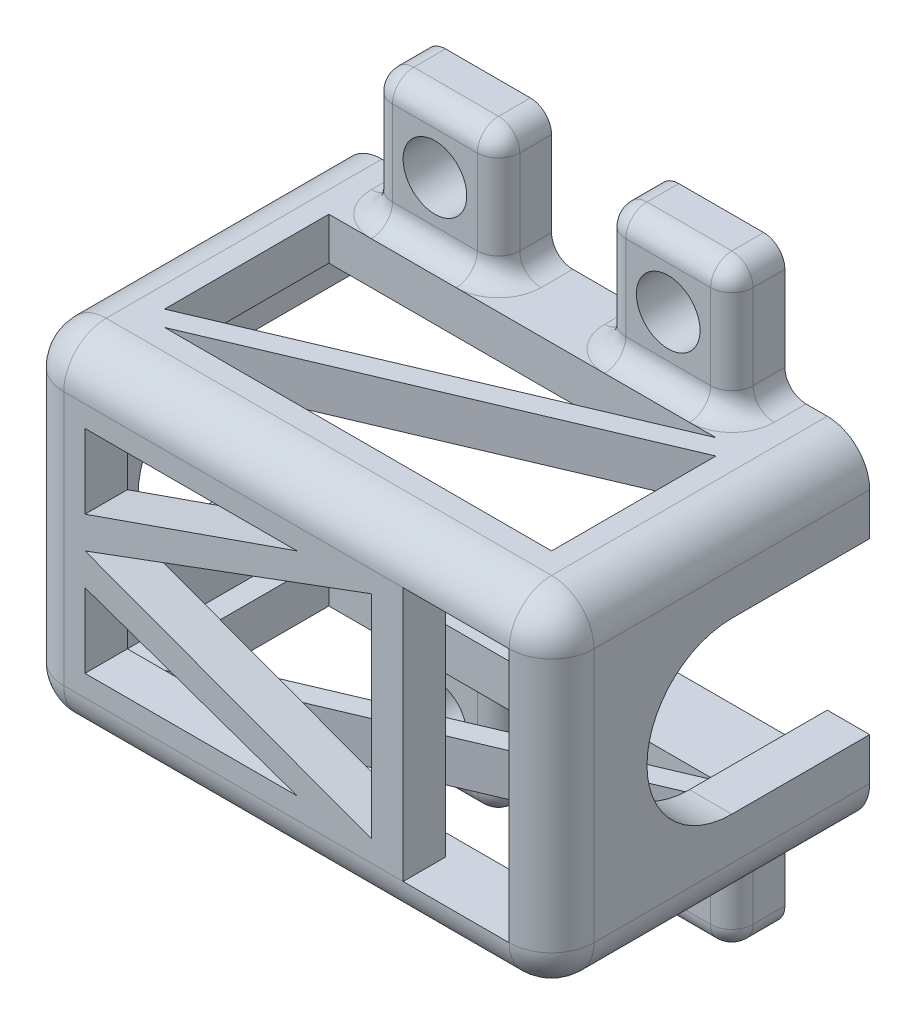
SolidWorks part; units mm, degrees
ref_plane "Alzado" through (0, 0, 0) normal (0, 0, 1) x (1, 0, 0)
ref_plane "Planta" through (0, 0, 0) normal (0, 1, 0) x (1, 0, 0)
ref_plane "Vista lateral" through (0, 0, 0) normal (1, 0, 0) x (0, 0, -1)
sketch "Croquis1" plane through (0, 0, 0) normal (0, 0, 1) x (1, 0, 0)
  line L1 (0, 0) -> (23, 0)
  line L2 (0, 0) -> (0, 16)
  line L3 (0, 16) -> (23, 16)
  line L4 (23, 0) -> (23, 16)
  dimension "D1" = 16
  dimension "D2" = 23
extrude "Saliente-Extruir1" add sketch "Croquis1" along normal blind 15
sketch "Croquis2" plane through (23, 0, 0) normal (1, 0, 0) x (0, 0, -1)
  line L0 (0, 0) -> (0, 16) construction
  line L1 (-13, 2) -> (-2, 2)
  line L2 (-13, 2) -> (-13, 14)
  line L3 (-13, 14) -> (-2, 14)
  line L4 (-2, 2) -> (-2, 14)
  line L5 (-15, 0) -> (-15, 16) construction
  line L6 (-15, 16) -> (0, 16) construction
  line L7 (-15, 0) -> (0, 0) construction
  dimension "D1" = 2
  dimension "D2" = 2
  dimension "D3" = 2
  dimension "D4" = 2
extrude "Cortar-Extruir1" cut sketch "Croquis2" against normal blind 21
sketch "Croquis4" plane through (0, 0, 0) normal (-1, 0, 0) x (0, 0, 1)
  line L0 (0, 0) -> (15, 16) construction
  line L1 (15, 16) -> (15, 0) construction
  line L2 (15, 16) -> (0, 16) construction
  line L3 (7.5, 12) -> (0, 12)
  line L4 (0, 16) -> (0, 0) construction
  line L5 (0, 12) -> (0, 4)
  line L6 (0, 4) -> (7.5, 4)
  arc A1 (7.5, 12) -> (7.5, 4) centre (7.5, 8) cw
  dimension "D1" = 4
  dimension "D3" = 8
  dimension "D2" = 7.5
extrude "Cortar-Extruir2" cut sketch "Croquis4" against normal blind 23
sketch "Croquis5" plane through (0, 0, 15) normal (0, 0, 1) x (1, 0, 0)
  line L0 (23, 0) -> (23, 16) construction
  line L1 (23, 2) -> (18, 2)
  line L2 (23, 2) -> (23, 14)
  line L3 (23, 14) -> (18, 14)
  line L4 (18, 2) -> (18, 14)
  line L5 (23, 16) -> (0, 16) construction
  line L6 (0, 0) -> (23, 0) construction
  dimension "D1" = 2
  dimension "D2" = 2
  dimension "D3" = 5
extrude "Cortar-Extruir3" cut sketch "Croquis5" against normal blind 2
fillet "Redondeo1" radius 2 5 edges at (11.5, 16, 15) (11.5, 0, 15) (0, 16, 7.5) (0, 8, 15) (0, 0, 7.5)
sketch "Croquis8" plane through (0, 0, 15) normal (0, 0, 1) x (1, 0, 0)
  line L0 (16.5, 3) -> (16.5, 13)
  line L1 (18, 14) -> (18, 2) construction
  line L2 (16.5, 8) -> (3, 8) construction
  line L3 (3, 8) -> (16.5, 3)
  line L4 (3, 8) -> (16.5, 13)
  line L6 (3, 8) -> (3, 6.5005) construction
  line L7 (3, 6.5005) -> (3, 3)
  line L8 (3, 3) -> (13, 3)
  line L9 (13, 3) -> (3, 6.5005)
  line L10 (3, 8) -> (3, 9.5) construction
  line L11 (3, 9.5) -> (3, 13)
  line L12 (3, 13) -> (13, 13)
  line L13 (13, 13) -> (3, 9.5)
  line L14 (18, 14) -> (2, 14) construction
  line L15 (2, 2) -> (18, 2) construction
  line L19 (2, 14) -> (2, 2) construction
  dimension "D1" = 1.5
  dimension "D2" = 1
  dimension "D3" = 1.4995
  dimension "D4" = 1.5
  dimension "D5" = 1
  dimension "D6" = 1
  dimension "D7" = 5
  dimension "D8" = 5
extrude "Cortar-Extruir4" cut sketch "Croquis8" against normal through all
sketch "Croquis18" plane through (0, 0, 2) normal (0, 0, 1) x (1, 0, 0)
  line L1 (2, 14) -> (23, 14)
  line L2 (2, 14) -> (2, 2)
  line L3 (2, 2) -> (23, 2)
  line L4 (23, 14) -> (23, 2)
extrude "Cortar-Extruir8" cut sketch "Croquis18" against normal through all
sketch "Croquis17" plane through (23, 0, 0) normal (1, 0, 0) x (0, 0, -1)
  line L1 (0, 0) -> (-15, 0)
  line L2 (0, 0) -> (0, 16)
  line L3 (0, 16) -> (-15, 16)
  line L4 (-15, 0) -> (-15, 16)
  dimension "D1" = 15
extrude "Saliente-Extruir7" add sketch "Croquis17" along normal blind 2
fillet "Redondeo8" radius 2 3 edges at (25, 0, 7.5) (25, 16, 7.5) (25, 8, 15)
sketch "Croquis19" plane through (0, 16, 0) normal (0, 1, 0) x (1, 0, 0)
  line L0 (23, 0) -> (2, 0) construction
  line L1 (21, 0) -> (15, 0)
  line L2 (21, 0) -> (21, -2.5)
  line L3 (21, -2.5) -> (15, -2.5)
  line L4 (15, 0) -> (15, -2.5)
  line L5 (23, -13) -> (23, 0) construction
  line L6 (4, 0) -> (10, 0)
  line L7 (4, 0) -> (4, -2.5)
  line L8 (4, -2.5) -> (10, -2.5)
  line L9 (10, 0) -> (10, -2.5)
  line L10 (2, 0) -> (2, -13) construction
  dimension "D1" = 2
  dimension "D2" = 2
  dimension "D3" = 2.5
  dimension "D4" = 2.5
  dimension "D5" = 6
  dimension "D6" = 6
extrude "Saliente-Extruir8" add sketch "Croquis19" along normal blind 6
sketch "Croquis20" plane through (0, 0, 0) normal (0, -1, 0) x (1, 0, 0)
  line L0 (2, 0) -> (23, 0) construction
  line L1 (4, 0) -> (10, 0)
  line L2 (4, 0) -> (4, 2.5)
  line L3 (4, 2.5) -> (10, 2.5)
  line L4 (10, 0) -> (10, 2.5)
  line L5 (2, 13) -> (2, 0) construction
  line L6 (21, 0) -> (15, 0)
  line L7 (21, 0) -> (21, 2.5)
  line L8 (21, 2.5) -> (15, 2.5)
  line L9 (15, 0) -> (15, 2.5)
  line L10 (23, 0) -> (23, 13) construction
  dimension "D1" = 2
  dimension "D2" = 2
  dimension "D3" = 2.5
  dimension "D4" = 2.5
  dimension "D5" = 6
  dimension "D6" = 6
extrude "Saliente-Extruir9" add sketch "Croquis20" along normal blind 6
sketch "Croquis21" plane through (0, 0, 2.5) normal (0, 0, 1) x (1, 0, 0)
  line L0 (4, 22) -> (10, 16) construction
  line L1 (15, 22) -> (21, 16) construction
  line L3 (21, 0) -> (15, -6) construction
  line L5 (10, 0) -> (4, -6) construction
  circle A0 centre (18, 19) radius 1.5
  circle A1 centre (7, 19) radius 1.5
  circle A2 centre (7, -3) radius 1.5
  circle A3 centre (18, -3) radius 1.5
  dimension "D1" = 3
  dimension "D2" = 3
  dimension "D3" = 3
  dimension "D4" = 3
extrude "Cortar-Extruir9" cut sketch "Croquis21" against normal through all
fillet "Redondeo9" radius 1 32 edges at (15, 0, 1.25) (21, 0, 1.25) (10, 0, 1.25) (4, 0, 1.25) (21, 16, 1.25) (15, 16, 1.25) (4, 16, 1.25) (10, 16, 1.25) (21, -6, 1.25) (15, -6, 1.25) (18, -6, 2.5) (15, -3, 2.5) (21, -3, 2.5) (18, 0, 2.5) (7, 0, 2.5) (10, -6, 1.25) (4, -6, 1.25) (4, -3, 2.5) (10, -3, 2.5) (7, -6, 2.5) (21, 22, 1.25) (15, 22, 1.25) (21, 19, 2.5) (18, 22, 2.5) (15, 19, 2.5) (18, 16, 2.5) (10, 22, 1.25) (4, 22, 1.25) (7, 16, 2.5) (4, 19, 2.5) (10, 19, 2.5) (7, 22, 2.5)
sketch "Croquis22" plane through (0, 0, 0) normal (0, -1, 0) x (1, 0, 0)
  line L1 (3, 3.5) -> (22, 3.5) construction
  line L6 (22, 3.5) -> (21.25, 3.5) construction
  line L9 (3, 4.25) -> (3, 3.5) construction
  line L10 (3, 3.5) -> (3.75, 3.5) construction
  line L12 (3, 11.25) -> (21.25, 3.5)
  line L13 (22, 11.25) -> (22, 12) construction
  line L14 (22, 12) -> (21.25, 12) construction
  line L15 (21.25, 3.5) -> (3, 3.5)
  line L16 (3, 3.5) -> (3, 11.25)
  line L17 (22, 4.25) -> (3.75, 12)
  line L18 (3.75, 12) -> (22, 12)
  line L19 (22, 12) -> (22, 4.25)
  line L20 (2, 13) -> (2, 0) construction
  line L21 (23, 0) -> (23, 13) construction
  line L22 (23, 13) -> (2, 13) construction
  line L23 (11, 0) -> (14, 0) construction
  point P5 (0, 0)
  dimension "D1" = 1.75
  dimension "D2" = 1.75
  dimension "D3" = 1
  dimension "D4" = 3.5
  dimension "D5" = 1
  dimension "D6" = 1
  dimension "D7" = 0.9835
extrude "Cortar-Extruir10" cut sketch "Croquis22" against normal blind 16
sketch "Croquis23" plane through (25, 0, 0) normal (1, 0, 0) x (0, 0, -1)
  line L0 (0, 8) -> (-6.5, 8) construction
  line L1 (0, 2) -> (0, 14) construction
  line L2 (-6.5, 8) -> (-6.5, 2) construction
  line L3 (-13, 2) -> (0, 2) construction
  line L4 (0, 8) -> (0, 4) construction
  line L5 (0, 4) -> (0, 12)
  line L6 (0, 12) -> (-6.5, 12)
  line L7 (0, 4) -> (-6.5, 4)
  arc A0 (-6.5, 4) -> (-6.5, 12) centre (-6.5, 8) cw
  dimension "D1" = 4
  dimension "D2" = 2
extrude "Cortar-Extruir11" cut sketch "Croquis23" against normal blind 2
